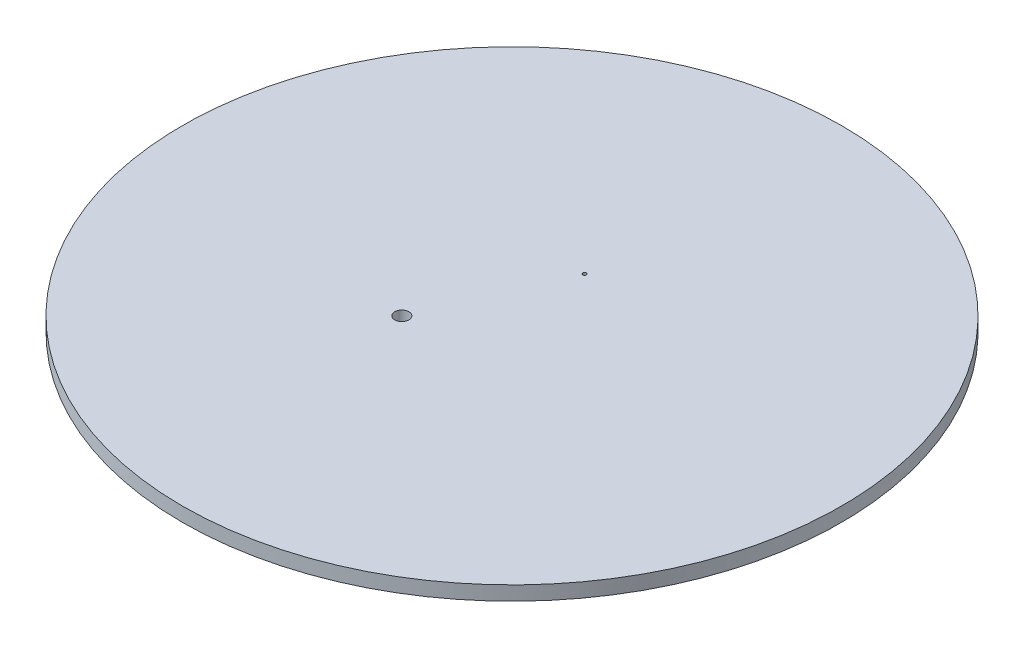
SolidWorks part; units mm, degrees
material "PTFE (general)"
ref_plane "Front Plane" through (0, 0, 0) normal (0, 0, 1) x (1, 0, 0)
ref_plane "Top Plane" through (0, 0, 0) normal (0, 1, 0) x (1, 0, 0)
ref_plane "Right Plane" through (0, 0, 0) normal (1, 0, 0) x (0, 0, -1)
sketch "Sketch1" plane through (0, 0, 0) normal (0, 1, 0) x (1, 0, 0)
  circle A0 centre (0, 0) radius 46.53
  dimension "D2" = 93.06
extrude "Boss-Extrude1" add sketch "Sketch1" along normal blind 2
sketch "Sketch2" plane through (0, 2, 0) normal (0, 1, 0) x (1, 0, 0)
  circle A0 centre (0, 10.25) radius 0.25
  dimension "D1" = 0.5
  dimension "D2" = 10.25
extrude "Cut-Extrude1" cut sketch "Sketch2" against normal through all both and the other way through all
sketch "Sketch3" plane through (0, 2, 0) normal (0, 1, 0) x (1, 0, 0)
  line L0 (0, 0) -> (-36.0536, 0) construction
  line L1 (0, 0) -> (0, 10.25) construction
  line L2 (0, 10.25) -> (0, 0) construction
  line L3 (0, 0) -> (-21.4265, -21.4265) construction
  circle A1 centre (-7.7782, -7.7782) radius 1
  dimension "D3" = 2
  dimension "D4" = 11
extrude "Cut-Extrude2" cut sketch "Sketch3" against normal through all both and the other way through all
